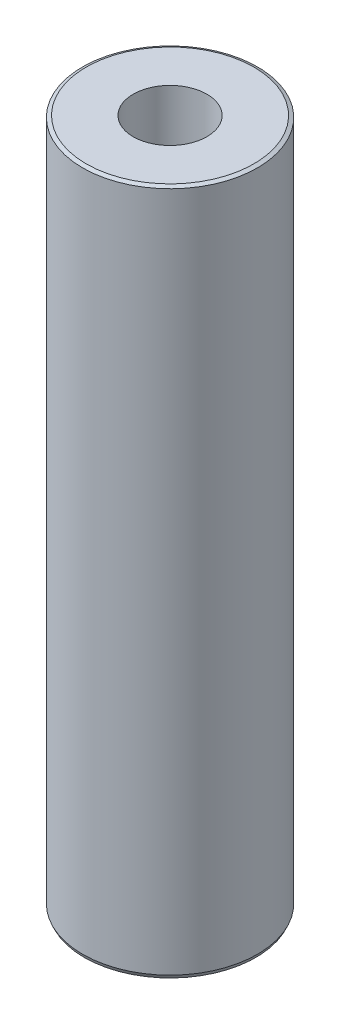
SolidWorks part; units mm, degrees
ref_plane "Front Plane" through (0, 0, 0) normal (0, 0, 1) x (1, 0, 0)
ref_plane "Top Plane" through (0, 0, 0) normal (0, 1, 0) x (1, 0, 0)
ref_plane "Right Plane" through (0, 0, 0) normal (1, 0, 0) x (0, 0, -1)
sketch "Sketch1" plane through (0, 0, 0) normal (0, 1, 0) x (1, 0, 0)
  circle A0 centre (0, 0) radius 57.5
  dimension "SHAFT_OD" = 115
extrude "Boss-Extrude1" add sketch "Sketch1" along normal blind 451.1319
sketch "Sketch2" plane through (0, 0, 0) normal (0, 1, 0) x (1, 0, 0)
  circle A0 centre (0, 0) radius 24.2234
  dimension "BORE_D" = 48.4467
extrude "Cut-Extrude1" cut sketch "Sketch2" along normal through all
chamfer "Chamfer1" distance 1.0859 angle 65.487 2 edges at (0, 451.1319, 57.5) (0, 0, 57.5) first distance on face at (0, 451.1319, 57.5) first distance on face at (0, 0, 24.2234)
